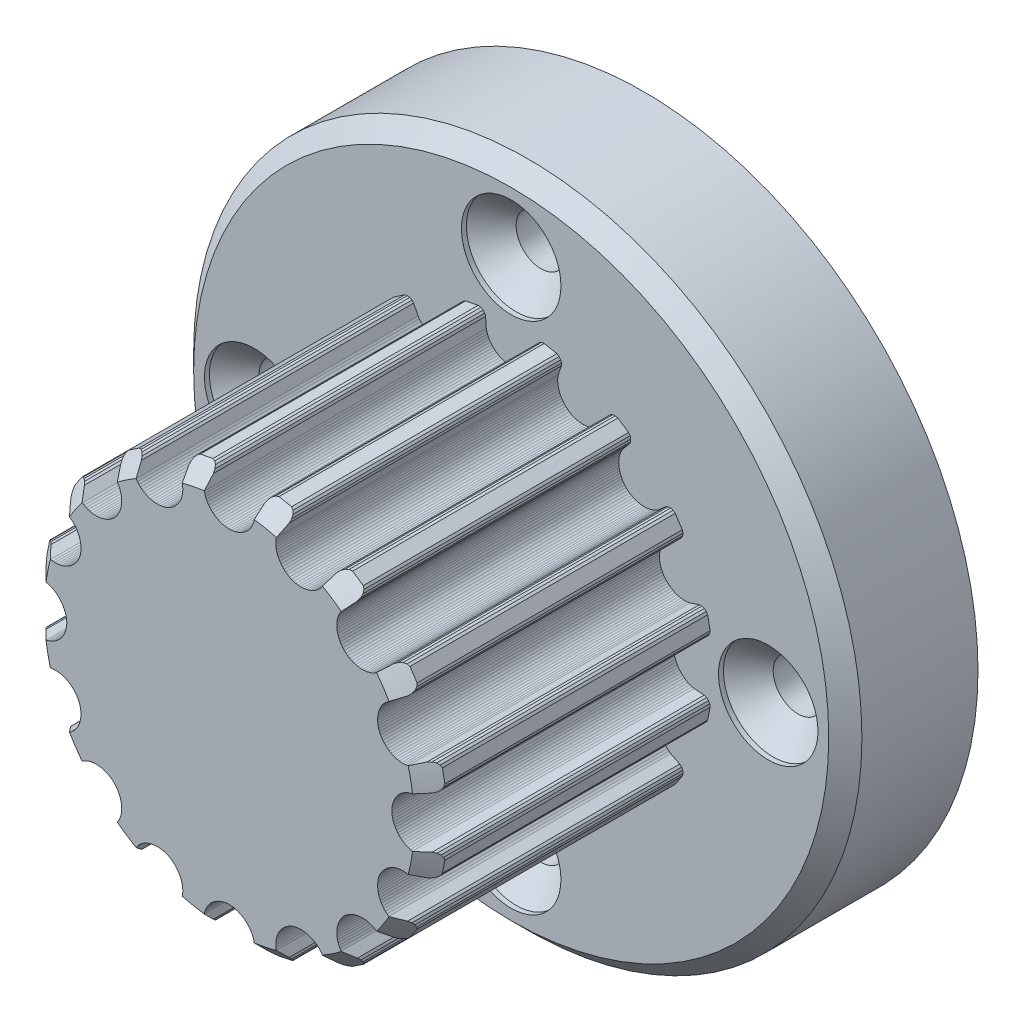
SolidWorks part; units mm, degrees
ref_plane "Front Plane" through (0, 0, 0) normal (0, 0, 1) x (1, 0, 0)
ref_plane "Top Plane" through (0, 0, 0) normal (0, 1, 0) x (1, 0, 0)
ref_plane "Right Plane" through (0, 0, 0) normal (1, 0, 0) x (0, 0, -1)
sketch "Sketch1" plane through (0, 0, 0) normal (0, 0, 1) x (1, 0, 0)
  circle A0 centre (0, 0) radius 15.5
  circle A1 centre (0, 15.5) radius 1.5
  circle A2 centre (15.5, 0) radius 1.5
  circle A3 centre (0, -15.5) radius 1.5
  circle A4 centre (-15.5, 0) radius 1.5
  circle A5 centre (0, 0) radius 20.15
  dimension "D1" = 31
  dimension "D2" = 3
  dimension "D3" = 40.3
extrude "Boss-Extrude1" add sketch "Sketch1" along normal blind 8 contours A5 A4 A0 A1 A2 A3 | A4 A0 A3 A2 A1 region at (0, 0, 0) region at (-19.5801, 0, 0)
sketch "Sketch8" plane through (0, 0, 8) normal (0, 0, 1) x (1, 0, 0)
  line L0 (-1.9904, -11.9969) -> (-1.8333, -11.9702)
  line L1 (-1.8333, -11.9702) -> (-1.6992, -11.8961)
  line L2 (-1.6992, -11.8961) -> (-1.5993, -11.7835)
  line L3 (-1.5993, -11.7835) -> (-1.5446, -11.6413)
  line L4 (-1.5446, -11.6413) -> (-1.5027, -11.0359)
  line L5 (-1.5027, -11.0359) -> (-1.4725, -10.9073)
  line L6 (-1.4725, -10.9073) -> (-1.4313, -10.7834)
  line L7 (-1.4313, -10.7834) -> (-1.3796, -10.6646)
  line L8 (-1.3796, -10.6646) -> (-1.3179, -10.5514)
  line L9 (-1.3179, -10.5514) -> (-1.2467, -10.4444)
  line L10 (-1.2467, -10.4444) -> (-1.1667, -10.3438)
  line L11 (-1.1667, -10.3438) -> (-1.0783, -10.2503)
  line L12 (-1.0783, -10.2503) -> (-0.9822, -10.1642)
  line L13 (-0.9822, -10.1642) -> (-0.8789, -10.086)
  line L14 (-0.8789, -10.086) -> (-0.7689, -10.0162)
  line L15 (-0.7689, -10.0162) -> (-0.6528, -9.9552)
  line L16 (-0.6528, -9.9552) -> (-0.5312, -9.9034)
  line L17 (-0.5312, -9.9034) -> (-0.4045, -9.8614)
  line L18 (-0.4045, -9.8614) -> (-0.2734, -9.8296)
  line L19 (-0.2734, -9.8296) -> (-0.1385, -9.8084)
  line L20 (-0.1385, -9.8084) -> (-0.0002, -9.7984)
  line L21 (-0.0002, -9.7984) -> (0.1382, -9.8084)
  line L22 (0.1382, -9.8084) -> (0.2733, -9.8295)
  line L23 (0.2733, -9.8295) -> (0.4045, -9.8613)
  line L24 (0.4045, -9.8613) -> (0.5312, -9.9032)
  line L25 (0.5312, -9.9032) -> (0.6529, -9.9549)
  line L26 (0.6529, -9.9549) -> (0.7691, -10.0159)
  line L27 (0.7691, -10.0159) -> (0.8791, -10.0858)
  line L28 (0.8791, -10.0858) -> (0.9825, -10.1639)
  line L29 (0.9825, -10.1639) -> (1.0786, -10.25)
  line L30 (1.0786, -10.25) -> (1.1669, -10.3436)
  line L31 (1.1669, -10.3436) -> (1.247, -10.4442)
  line L32 (1.247, -10.4442) -> (1.3181, -10.5512)
  line L33 (1.3181, -10.5512) -> (1.3798, -10.6644)
  line L34 (1.3798, -10.6644) -> (1.4315, -10.7832)
  line L35 (1.4315, -10.7832) -> (1.4726, -10.9072)
  line L36 (1.4726, -10.9072) -> (1.5027, -11.0359)
  line L37 (1.5027, -11.0359) -> (1.5446, -11.6413)
  line L38 (1.5446, -11.6413) -> (1.5993, -11.7835)
  line L39 (1.5993, -11.7835) -> (1.6992, -11.8961)
  line L40 (1.6992, -11.8961) -> (1.8333, -11.9702)
  line L41 (1.8333, -11.9702) -> (1.9904, -11.9969)
  line L42 (1.9904, -11.9969) -> (2.7522, -11.8454)
  line L43 (2.7522, -11.8454) -> (2.8871, -11.7606)
  line L44 (2.8871, -11.7606) -> (2.9825, -11.6408)
  line L45 (2.9825, -11.6408) -> (3.0317, -11.4985)
  line L46 (3.0317, -11.4985) -> (3.0279, -11.3462)
  line L47 (3.0279, -11.3462) -> (2.835, -10.7709)
  line L48 (2.835, -10.7709) -> (2.8136, -10.6405)
  line L49 (2.8136, -10.6405) -> (2.8042, -10.5103)
  line L50 (2.8042, -10.5103) -> (2.8066, -10.3807)
  line L51 (2.8066, -10.3807) -> (2.8203, -10.2526)
  line L52 (2.8203, -10.2526) -> (2.8451, -10.1264)
  line L53 (2.8451, -10.1264) -> (2.8805, -10.0029)
  line L54 (2.8805, -10.0029) -> (2.9264, -9.8827)
  line L55 (2.9264, -9.8827) -> (2.9822, -9.7664)
  line L56 (2.9822, -9.7664) -> (3.0478, -9.6546)
  line L57 (3.0478, -9.6546) -> (3.1227, -9.548)
  line L58 (3.1227, -9.548) -> (3.2066, -9.4472)
  line L59 (3.2066, -9.4472) -> (3.2992, -9.3528)
  line L60 (3.2992, -9.3528) -> (3.4001, -9.2656)
  line L61 (3.4001, -9.2656) -> (3.509, -9.186)
  line L62 (3.509, -9.186) -> (3.6256, -9.1148)
  line L63 (3.6256, -9.1148) -> (3.7495, -9.0526)
  line L64 (3.7495, -9.0526) -> (3.8812, -9.0089)
  line L65 (3.8812, -9.0089) -> (4.0141, -8.9767)
  line L66 (4.0141, -8.9767) -> (4.1474, -8.9558)
  line L67 (4.1474, -8.9558) -> (4.2806, -8.9461)
  line L68 (4.2806, -8.9461) -> (4.4128, -8.9473)
  line L69 (4.4128, -8.9473) -> (4.5435, -8.9592)
  line L70 (4.5435, -8.9592) -> (4.6718, -8.9816)
  line L71 (4.6718, -8.9816) -> (4.7972, -9.0143)
  line L72 (4.7972, -9.0143) -> (4.919, -9.057)
  line L73 (4.919, -9.057) -> (5.0364, -9.1097)
  line L74 (5.0364, -9.1097) -> (5.1488, -9.1719)
  line L75 (5.1488, -9.1719) -> (5.2555, -9.2437)
  line L76 (5.2555, -9.2437) -> (5.3558, -9.3246)
  line L77 (5.3558, -9.3246) -> (5.4491, -9.4146)
  line L78 (5.4491, -9.4146) -> (5.5345, -9.5134)
  line L79 (5.5345, -9.5134) -> (5.6115, -9.6208)
  line L80 (5.6115, -9.6208) -> (5.882, -10.164)
  line L81 (5.882, -10.164) -> (5.9869, -10.2745)
  line L82 (5.9869, -10.2745) -> (6.1223, -10.3403)
  line L83 (6.1223, -10.3403) -> (6.2745, -10.3575)
  line L84 (6.2745, -10.3575) -> (6.4299, -10.322)
  line L85 (6.4299, -10.322) -> (7.0757, -9.8905)
  line L86 (7.0757, -9.8905) -> (7.1679, -9.7605)
  line L87 (7.1679, -9.7605) -> (7.2103, -9.6133)
  line L88 (7.2103, -9.6133) -> (7.2013, -9.4631)
  line L89 (7.2013, -9.4631) -> (7.1394, -9.3238)
  line L90 (7.1394, -9.3238) -> (6.741, -8.8661)
  line L91 (6.741, -8.8661) -> (6.6714, -8.7539)
  line L92 (6.6714, -8.7539) -> (6.6129, -8.6371)
  line L93 (6.6129, -8.6371) -> (6.5655, -8.5165)
  line L94 (6.5655, -8.5165) -> (6.5291, -8.3929)
  line L95 (6.5291, -8.3929) -> (6.5037, -8.2669)
  line L96 (6.5037, -8.2669) -> (6.4892, -8.1392)
  line L97 (6.4892, -8.1392) -> (6.4856, -8.0106)
  line L98 (6.4856, -8.0106) -> (6.4926, -7.8817)
  line L99 (6.4926, -7.8817) -> (6.5104, -7.7534)
  line L100 (6.5104, -7.7534) -> (6.5388, -7.6262)
  line L101 (6.5388, -7.6262) -> (6.5778, -7.501)
  line L102 (6.5778, -7.501) -> (6.6272, -7.3784)
  line L103 (6.6272, -7.3784) -> (6.687, -7.2591)
  line L104 (6.687, -7.2591) -> (6.7572, -7.1439)
  line L105 (6.7572, -7.1439) -> (6.8377, -7.0335)
  line L106 (6.8377, -7.0335) -> (6.9284, -6.9286)
  line L107 (6.9284, -6.9286) -> (7.0333, -6.8378)
  line L108 (7.0333, -6.8378) -> (7.1438, -6.7572)
  line L109 (7.1438, -6.7572) -> (7.259, -6.6869)
  line L110 (7.259, -6.6869) -> (7.3783, -6.627)
  line L111 (7.3783, -6.627) -> (7.5009, -6.5775)
  line L112 (7.5009, -6.5775) -> (7.6262, -6.5385)
  line L113 (7.6262, -6.5385) -> (7.7533, -6.5101)
  line L114 (7.7533, -6.5101) -> (7.8817, -6.4923)
  line L115 (7.8817, -6.4923) -> (8.0105, -6.4852)
  line L116 (8.0105, -6.4852) -> (8.1392, -6.4889)
  line L117 (8.1392, -6.4889) -> (8.2669, -6.5034)
  line L118 (8.2669, -6.5034) -> (8.3929, -6.5288)
  line L119 (8.3929, -6.5288) -> (8.5165, -6.5652)
  line L120 (8.5165, -6.5652) -> (8.6371, -6.6127)
  line L121 (8.6371, -6.6127) -> (8.7539, -6.6713)
  line L122 (8.7539, -6.6713) -> (8.8661, -6.741)
  line L123 (8.8661, -6.741) -> (9.3238, -7.1394)
  line L124 (9.3238, -7.1394) -> (9.4631, -7.2013)
  line L125 (9.4631, -7.2013) -> (9.6133, -7.2103)
  line L126 (9.6133, -7.2103) -> (9.7605, -7.1679)
  line L127 (9.7605, -7.1679) -> (9.8905, -7.0757)
  line L128 (9.8905, -7.0757) -> (10.322, -6.4299)
  line L129 (10.322, -6.4299) -> (10.3575, -6.2745)
  line L130 (10.3575, -6.2745) -> (10.3403, -6.1223)
  line L131 (10.3403, -6.1223) -> (10.2745, -5.9869)
  line L132 (10.2745, -5.9869) -> (10.164, -5.882)
  line L133 (10.164, -5.882) -> (9.6208, -5.6115)
  line L134 (9.6208, -5.6115) -> (9.5135, -5.5345)
  line L135 (9.5135, -5.5345) -> (9.4148, -5.449)
  line L136 (9.4148, -5.449) -> (9.3248, -5.3558)
  line L137 (9.3248, -5.3558) -> (9.2439, -5.2554)
  line L138 (9.2439, -5.2554) -> (9.1722, -5.1487)
  line L139 (9.1722, -5.1487) -> (9.11, -5.0363)
  line L140 (9.11, -5.0363) -> (9.0574, -4.9189)
  line L141 (9.0574, -4.9189) -> (9.0146, -4.7971)
  line L142 (9.0146, -4.7971) -> (8.9819, -4.6717)
  line L143 (8.9819, -4.6717) -> (8.9595, -4.5434)
  line L144 (8.9595, -4.5434) -> (8.9476, -4.4128)
  line L145 (8.9476, -4.4128) -> (8.9463, -4.2806)
  line L146 (8.9463, -4.2806) -> (8.956, -4.1475)
  line L147 (8.956, -4.1475) -> (8.9767, -4.0143)
  line L148 (8.9767, -4.0143) -> (9.0088, -3.8815)
  line L149 (9.0088, -3.8815) -> (9.0524, -3.7498)
  line L150 (9.0524, -3.7498) -> (9.1147, -3.6258)
  line L151 (9.1147, -3.6258) -> (9.1859, -3.5091)
  line L152 (9.1859, -3.5091) -> (9.2654, -3.4)
  line L153 (9.2654, -3.4) -> (9.3527, -3.299)
  line L154 (9.3527, -3.299) -> (9.447, -3.2064)
  line L155 (9.447, -3.2064) -> (9.5478, -3.1224)
  line L156 (9.5478, -3.1224) -> (9.6544, -3.0475)
  line L157 (9.6544, -3.0475) -> (9.7662, -2.9819)
  line L158 (9.7662, -2.9819) -> (9.8826, -2.926)
  line L159 (9.8826, -2.926) -> (10.0028, -2.8802)
  line L160 (10.0028, -2.8802) -> (10.1263, -2.8448)
  line L161 (10.1263, -2.8448) -> (10.2525, -2.82)
  line L162 (10.2525, -2.82) -> (10.3807, -2.8064)
  line L163 (10.3807, -2.8064) -> (10.5102, -2.8041)
  line L164 (10.5102, -2.8041) -> (10.6405, -2.8135)
  line L165 (10.6405, -2.8135) -> (10.7709, -2.835)
  line L166 (10.7709, -2.835) -> (11.3462, -3.0279)
  line L167 (11.3462, -3.0279) -> (11.4985, -3.0317)
  line L168 (11.4985, -3.0317) -> (11.6408, -2.9825)
  line L169 (11.6408, -2.9825) -> (11.7606, -2.8871)
  line L170 (11.7606, -2.8871) -> (11.8454, -2.7522)
  line L171 (11.8454, -2.7522) -> (11.9969, -1.9904)
  line L172 (11.9969, -1.9904) -> (11.9702, -1.8333)
  line L173 (11.9702, -1.8333) -> (11.8961, -1.6992)
  line L174 (11.8961, -1.6992) -> (11.7835, -1.5993)
  line L175 (11.7835, -1.5993) -> (11.6413, -1.5446)
  line L176 (11.6413, -1.5446) -> (11.0359, -1.5027)
  line L177 (11.0359, -1.5027) -> (10.9073, -1.4725)
  line L178 (10.9073, -1.4725) -> (10.7834, -1.4313)
  line L179 (10.7834, -1.4313) -> (10.6646, -1.3796)
  line L180 (10.6646, -1.3796) -> (10.5514, -1.3179)
  line L181 (10.5514, -1.3179) -> (10.4444, -1.2467)
  line L182 (10.4444, -1.2467) -> (10.3438, -1.1667)
  line L183 (10.3438, -1.1667) -> (10.2503, -1.0783)
  line L184 (10.2503, -1.0783) -> (10.1642, -0.9822)
  line L185 (10.1642, -0.9822) -> (10.086, -0.8789)
  line L186 (10.086, -0.8789) -> (10.0162, -0.7689)
  line L187 (10.0162, -0.7689) -> (9.9552, -0.6528)
  line L188 (9.9552, -0.6528) -> (9.9034, -0.5312)
  line L189 (9.9034, -0.5312) -> (9.8614, -0.4045)
  line L190 (9.8614, -0.4045) -> (9.8296, -0.2734)
  line L191 (9.8296, -0.2734) -> (9.8084, -0.1385)
  line L192 (9.8084, -0.1385) -> (9.7984, -0.0002)
  line L193 (9.7984, -0.0002) -> (9.8084, 0.1382)
  line L194 (9.8084, 0.1382) -> (9.8295, 0.2733)
  line L195 (9.8295, 0.2733) -> (9.8613, 0.4045)
  line L196 (9.8613, 0.4045) -> (9.9032, 0.5312)
  line L197 (9.9032, 0.5312) -> (9.9549, 0.6529)
  line L198 (9.9549, 0.6529) -> (10.0159, 0.7691)
  line L199 (10.0159, 0.7691) -> (10.0858, 0.8791)
  line L200 (10.0858, 0.8791) -> (10.1639, 0.9825)
  line L201 (10.1639, 0.9825) -> (10.25, 1.0786)
  line L202 (10.25, 1.0786) -> (10.3436, 1.1669)
  line L203 (10.3436, 1.1669) -> (10.4442, 1.247)
  line L204 (10.4442, 1.247) -> (10.5512, 1.3181)
  line L205 (10.5512, 1.3181) -> (10.6644, 1.3798)
  line L206 (10.6644, 1.3798) -> (10.7832, 1.4315)
  line L207 (10.7832, 1.4315) -> (10.9072, 1.4726)
  line L208 (10.9072, 1.4726) -> (11.0359, 1.5027)
  line L209 (11.0359, 1.5027) -> (11.6413, 1.5446)
  line L210 (11.6413, 1.5446) -> (11.7835, 1.5993)
  line L211 (11.7835, 1.5993) -> (11.8961, 1.6992)
  line L212 (11.8961, 1.6992) -> (11.9702, 1.8333)
  line L213 (11.9702, 1.8333) -> (11.9969, 1.9904)
  line L214 (11.9969, 1.9904) -> (11.8454, 2.7522)
  line L215 (11.8454, 2.7522) -> (11.7606, 2.8871)
  line L216 (11.7606, 2.8871) -> (11.6408, 2.9825)
  line L217 (11.6408, 2.9825) -> (11.4985, 3.0317)
  line L218 (11.4985, 3.0317) -> (11.3462, 3.0279)
  line L219 (11.3462, 3.0279) -> (10.7709, 2.835)
  line L220 (10.7709, 2.835) -> (10.6405, 2.8136)
  line L221 (10.6405, 2.8136) -> (10.5103, 2.8042)
  line L222 (10.5103, 2.8042) -> (10.3807, 2.8066)
  line L223 (10.3807, 2.8066) -> (10.2526, 2.8203)
  line L224 (10.2526, 2.8203) -> (10.1264, 2.8451)
  line L225 (10.1264, 2.8451) -> (10.0029, 2.8805)
  line L226 (10.0029, 2.8805) -> (9.8827, 2.9264)
  line L227 (9.8827, 2.9264) -> (9.7664, 2.9822)
  line L228 (9.7664, 2.9822) -> (9.6546, 3.0478)
  line L229 (9.6546, 3.0478) -> (9.548, 3.1227)
  line L230 (9.548, 3.1227) -> (9.4472, 3.2066)
  line L231 (9.4472, 3.2066) -> (9.3528, 3.2992)
  line L232 (9.3528, 3.2992) -> (9.2656, 3.4001)
  line L233 (9.2656, 3.4001) -> (9.186, 3.509)
  line L234 (9.186, 3.509) -> (9.1148, 3.6256)
  line L235 (9.1148, 3.6256) -> (9.0526, 3.7495)
  line L236 (9.0526, 3.7495) -> (9.0089, 3.8812)
  line L237 (9.0089, 3.8812) -> (8.9767, 4.0141)
  line L238 (8.9767, 4.0141) -> (8.9558, 4.1474)
  line L239 (8.9558, 4.1474) -> (8.9461, 4.2806)
  line L240 (8.9461, 4.2806) -> (8.9473, 4.4128)
  line L241 (8.9473, 4.4128) -> (8.9592, 4.5435)
  line L242 (8.9592, 4.5435) -> (8.9816, 4.6718)
  line L243 (8.9816, 4.6718) -> (9.0143, 4.7972)
  line L244 (9.0143, 4.7972) -> (9.057, 4.919)
  line L245 (9.057, 4.919) -> (9.1097, 5.0364)
  line L246 (9.1097, 5.0364) -> (9.1719, 5.1488)
  line L247 (9.1719, 5.1488) -> (9.2437, 5.2555)
  line L248 (9.2437, 5.2555) -> (9.3246, 5.3558)
  line L249 (9.3246, 5.3558) -> (9.4146, 5.4491)
  line L250 (9.4146, 5.4491) -> (9.5134, 5.5345)
  line L251 (9.5134, 5.5345) -> (9.6208, 5.6115)
  line L252 (9.6208, 5.6115) -> (10.164, 5.882)
  line L253 (10.164, 5.882) -> (10.2745, 5.9869)
  line L254 (10.2745, 5.9869) -> (10.3403, 6.1223)
  line L255 (10.3403, 6.1223) -> (10.3575, 6.2745)
  line L256 (10.3575, 6.2745) -> (10.322, 6.4299)
  line L257 (10.322, 6.4299) -> (9.8905, 7.0757)
  line L258 (9.8905, 7.0757) -> (9.7605, 7.1679)
  line L259 (9.7605, 7.1679) -> (9.6133, 7.2103)
  line L260 (9.6133, 7.2103) -> (9.4631, 7.2013)
  line L261 (9.4631, 7.2013) -> (9.3238, 7.1394)
  line L262 (9.3238, 7.1394) -> (8.8661, 6.741)
  line L263 (8.8661, 6.741) -> (8.7539, 6.6714)
  line L264 (8.7539, 6.6714) -> (8.6371, 6.6129)
  line L265 (8.6371, 6.6129) -> (8.5165, 6.5655)
  line L266 (8.5165, 6.5655) -> (8.3929, 6.5291)
  line L267 (8.3929, 6.5291) -> (8.2669, 6.5037)
  line L268 (8.2669, 6.5037) -> (8.1392, 6.4892)
  line L269 (8.1392, 6.4892) -> (8.0106, 6.4856)
  line L270 (8.0106, 6.4856) -> (7.8817, 6.4926)
  line L271 (7.8817, 6.4926) -> (7.7534, 6.5104)
  line L272 (7.7534, 6.5104) -> (7.6262, 6.5388)
  line L273 (7.6262, 6.5388) -> (7.501, 6.5778)
  line L274 (7.501, 6.5778) -> (7.3784, 6.6272)
  line L275 (7.3784, 6.6272) -> (7.2591, 6.687)
  line L276 (7.2591, 6.687) -> (7.1439, 6.7572)
  line L277 (7.1439, 6.7572) -> (7.0335, 6.8377)
  line L278 (7.0335, 6.8377) -> (6.9286, 6.9284)
  line L279 (6.9286, 6.9284) -> (6.8378, 7.0333)
  line L280 (6.8378, 7.0333) -> (6.7572, 7.1438)
  line L281 (6.7572, 7.1438) -> (6.6869, 7.259)
  line L282 (6.6869, 7.259) -> (6.627, 7.3783)
  line L283 (6.627, 7.3783) -> (6.5775, 7.5009)
  line L284 (6.5775, 7.5009) -> (6.5385, 7.6262)
  line L285 (6.5385, 7.6262) -> (6.5101, 7.7533)
  line L286 (6.5101, 7.7533) -> (6.4923, 7.8817)
  line L287 (6.4923, 7.8817) -> (6.4852, 8.0105)
  line L288 (6.4852, 8.0105) -> (6.4889, 8.1392)
  line L289 (6.4889, 8.1392) -> (6.5034, 8.2669)
  line L290 (6.5034, 8.2669) -> (6.5288, 8.3929)
  line L291 (6.5288, 8.3929) -> (6.5652, 8.5165)
  line L292 (6.5652, 8.5165) -> (6.6127, 8.6371)
  line L293 (6.6127, 8.6371) -> (6.6713, 8.7539)
  line L294 (6.6713, 8.7539) -> (6.741, 8.8661)
  line L295 (6.741, 8.8661) -> (7.1394, 9.3238)
  line L296 (7.1394, 9.3238) -> (7.2013, 9.4631)
  line L297 (7.2013, 9.4631) -> (7.2103, 9.6133)
  line L298 (7.2103, 9.6133) -> (7.1679, 9.7605)
  line L299 (7.1679, 9.7605) -> (7.0757, 9.8905)
  line L300 (7.0757, 9.8905) -> (6.4299, 10.322)
  line L301 (6.4299, 10.322) -> (6.2745, 10.3575)
  line L302 (6.2745, 10.3575) -> (6.1223, 10.3403)
  line L303 (6.1223, 10.3403) -> (5.9869, 10.2745)
  line L304 (5.9869, 10.2745) -> (5.882, 10.164)
  line L305 (5.882, 10.164) -> (5.6115, 9.6208)
  line L306 (5.6115, 9.6208) -> (5.5345, 9.5135)
  line L307 (5.5345, 9.5135) -> (5.449, 9.4148)
  line L308 (5.449, 9.4148) -> (5.3558, 9.3248)
  line L309 (5.3558, 9.3248) -> (5.2554, 9.2439)
  line L310 (5.2554, 9.2439) -> (5.1487, 9.1722)
  line L311 (5.1487, 9.1722) -> (5.0363, 9.11)
  line L312 (5.0363, 9.11) -> (4.9189, 9.0574)
  line L313 (4.9189, 9.0574) -> (4.7971, 9.0146)
  line L314 (4.7971, 9.0146) -> (4.6717, 8.9819)
  line L315 (4.6717, 8.9819) -> (4.5434, 8.9595)
  line L316 (4.5434, 8.9595) -> (4.4128, 8.9476)
  line L317 (4.4128, 8.9476) -> (4.2806, 8.9463)
  line L318 (4.2806, 8.9463) -> (4.1475, 8.956)
  line L319 (4.1475, 8.956) -> (4.0143, 8.9767)
  line L320 (4.0143, 8.9767) -> (3.8815, 9.0088)
  line L321 (3.8815, 9.0088) -> (3.7498, 9.0524)
  line L322 (3.7498, 9.0524) -> (3.6258, 9.1147)
  line L323 (3.6258, 9.1147) -> (3.5091, 9.1859)
  line L324 (3.5091, 9.1859) -> (3.4, 9.2654)
  line L325 (3.4, 9.2654) -> (3.299, 9.3527)
  line L326 (3.299, 9.3527) -> (3.2064, 9.447)
  line L327 (3.2064, 9.447) -> (3.1224, 9.5478)
  line L328 (3.1224, 9.5478) -> (3.0475, 9.6544)
  line L329 (3.0475, 9.6544) -> (2.9819, 9.7662)
  line L330 (2.9819, 9.7662) -> (2.926, 9.8826)
  line L331 (2.926, 9.8826) -> (2.8802, 10.0028)
  line L332 (2.8802, 10.0028) -> (2.8448, 10.1263)
  line L333 (2.8448, 10.1263) -> (2.82, 10.2525)
  line L334 (2.82, 10.2525) -> (2.8064, 10.3807)
  line L335 (2.8064, 10.3807) -> (2.8041, 10.5102)
  line L336 (2.8041, 10.5102) -> (2.8135, 10.6405)
  line L337 (2.8135, 10.6405) -> (2.835, 10.7709)
  line L338 (2.835, 10.7709) -> (3.0279, 11.3462)
  line L339 (3.0279, 11.3462) -> (3.0317, 11.4985)
  line L340 (3.0317, 11.4985) -> (2.9825, 11.6408)
  line L341 (2.9825, 11.6408) -> (2.8871, 11.7606)
  line L342 (2.8871, 11.7606) -> (2.7522, 11.8454)
  line L343 (2.7522, 11.8454) -> (1.9904, 11.9969)
  line L344 (1.9904, 11.9969) -> (1.8333, 11.9702)
  line L345 (1.8333, 11.9702) -> (1.6992, 11.8961)
  line L346 (1.6992, 11.8961) -> (1.5993, 11.7835)
  line L347 (1.5993, 11.7835) -> (1.5446, 11.6413)
  line L348 (1.5446, 11.6413) -> (1.5027, 11.0359)
  line L349 (1.5027, 11.0359) -> (1.4725, 10.9073)
  line L350 (1.4725, 10.9073) -> (1.4313, 10.7834)
  line L351 (1.4313, 10.7834) -> (1.3796, 10.6646)
  line L352 (1.3796, 10.6646) -> (1.3179, 10.5514)
  line L353 (1.3179, 10.5514) -> (1.2467, 10.4444)
  line L354 (1.2467, 10.4444) -> (1.1667, 10.3438)
  line L355 (1.1667, 10.3438) -> (1.0783, 10.2503)
  line L356 (1.0783, 10.2503) -> (0.9822, 10.1642)
  line L357 (0.9822, 10.1642) -> (0.8789, 10.086)
  line L358 (0.8789, 10.086) -> (0.7689, 10.0162)
  line L359 (0.7689, 10.0162) -> (0.6528, 9.9552)
  line L360 (0.6528, 9.9552) -> (0.5312, 9.9034)
  line L361 (0.5312, 9.9034) -> (0.4045, 9.8614)
  line L362 (0.4045, 9.8614) -> (0.2734, 9.8296)
  line L363 (0.2734, 9.8296) -> (0.1385, 9.8084)
  line L364 (0.1385, 9.8084) -> (0.0002, 9.7984)
  line L365 (0.0002, 9.7984) -> (-0.1382, 9.8084)
  line L366 (-0.1382, 9.8084) -> (-0.2733, 9.8295)
  line L367 (-0.2733, 9.8295) -> (-0.4045, 9.8613)
  line L368 (-0.4045, 9.8613) -> (-0.5312, 9.9032)
  line L369 (-0.5312, 9.9032) -> (-0.6529, 9.9549)
  line L370 (-0.6529, 9.9549) -> (-0.7691, 10.0159)
  line L371 (-0.7691, 10.0159) -> (-0.8791, 10.0858)
  line L372 (-0.8791, 10.0858) -> (-0.9825, 10.1639)
  line L373 (-0.9825, 10.1639) -> (-1.0786, 10.25)
  line L374 (-1.0786, 10.25) -> (-1.1669, 10.3436)
  line L375 (-1.1669, 10.3436) -> (-1.247, 10.4442)
  line L376 (-1.247, 10.4442) -> (-1.3181, 10.5512)
  line L377 (-1.3181, 10.5512) -> (-1.3798, 10.6644)
  line L378 (-1.3798, 10.6644) -> (-1.4315, 10.7832)
  line L379 (-1.4315, 10.7832) -> (-1.4726, 10.9072)
  line L380 (-1.4726, 10.9072) -> (-1.5027, 11.0359)
  line L381 (-1.5027, 11.0359) -> (-1.5446, 11.6413)
  line L382 (-1.5446, 11.6413) -> (-1.5993, 11.7835)
  line L383 (-1.5993, 11.7835) -> (-1.6992, 11.8961)
  line L384 (-1.6992, 11.8961) -> (-1.8333, 11.9702)
  line L385 (-1.8333, 11.9702) -> (-1.9904, 11.9969)
  line L386 (-1.9904, 11.9969) -> (-2.7522, 11.8454)
  line L387 (-2.7522, 11.8454) -> (-2.8871, 11.7606)
  line L388 (-2.8871, 11.7606) -> (-2.9825, 11.6408)
  line L389 (-2.9825, 11.6408) -> (-3.0317, 11.4985)
  line L390 (-3.0317, 11.4985) -> (-3.0279, 11.3462)
  line L391 (-3.0279, 11.3462) -> (-2.835, 10.7709)
  line L392 (-2.835, 10.7709) -> (-2.8136, 10.6405)
  line L393 (-2.8136, 10.6405) -> (-2.8042, 10.5103)
  line L394 (-2.8042, 10.5103) -> (-2.8066, 10.3807)
  line L395 (-2.8066, 10.3807) -> (-2.8203, 10.2526)
  line L396 (-2.8203, 10.2526) -> (-2.8451, 10.1264)
  line L397 (-2.8451, 10.1264) -> (-2.8805, 10.0029)
  line L398 (-2.8805, 10.0029) -> (-2.9264, 9.8827)
  line L399 (-2.9264, 9.8827) -> (-2.9822, 9.7664)
  line L400 (-2.9822, 9.7664) -> (-3.0478, 9.6546)
  line L401 (-3.0478, 9.6546) -> (-3.1227, 9.548)
  line L402 (-3.1227, 9.548) -> (-3.2066, 9.4472)
  line L403 (-3.2066, 9.4472) -> (-3.2992, 9.3528)
  line L404 (-3.2992, 9.3528) -> (-3.4001, 9.2656)
  line L405 (-3.4001, 9.2656) -> (-3.509, 9.186)
  line L406 (-3.509, 9.186) -> (-3.6256, 9.1148)
  line L407 (-3.6256, 9.1148) -> (-3.7495, 9.0526)
  line L408 (-3.7495, 9.0526) -> (-3.8812, 9.0089)
  line L409 (-3.8812, 9.0089) -> (-4.0141, 8.9767)
  line L410 (-4.0141, 8.9767) -> (-4.1474, 8.9558)
  line L411 (-4.1474, 8.9558) -> (-4.2806, 8.9461)
  line L412 (-4.2806, 8.9461) -> (-4.4128, 8.9473)
  line L413 (-4.4128, 8.9473) -> (-4.5435, 8.9592)
  line L414 (-4.5435, 8.9592) -> (-4.6718, 8.9816)
  line L415 (-4.6718, 8.9816) -> (-4.7972, 9.0143)
  line L416 (-4.7972, 9.0143) -> (-4.919, 9.057)
  line L417 (-4.919, 9.057) -> (-5.0364, 9.1097)
  line L418 (-5.0364, 9.1097) -> (-5.1488, 9.1719)
  line L419 (-5.1488, 9.1719) -> (-5.2555, 9.2437)
  line L420 (-5.2555, 9.2437) -> (-5.3558, 9.3246)
  line L421 (-5.3558, 9.3246) -> (-5.4491, 9.4146)
  line L422 (-5.4491, 9.4146) -> (-5.5345, 9.5134)
  line L423 (-5.5345, 9.5134) -> (-5.6115, 9.6208)
  line L424 (-5.6115, 9.6208) -> (-5.882, 10.164)
  line L425 (-5.882, 10.164) -> (-5.9869, 10.2745)
  line L426 (-5.9869, 10.2745) -> (-6.1223, 10.3403)
  line L427 (-6.1223, 10.3403) -> (-6.2745, 10.3575)
  line L428 (-6.2745, 10.3575) -> (-6.4299, 10.322)
  line L429 (-6.4299, 10.322) -> (-7.0757, 9.8905)
  line L430 (-7.0757, 9.8905) -> (-7.1679, 9.7605)
  line L431 (-7.1679, 9.7605) -> (-7.2103, 9.6133)
  line L432 (-7.2103, 9.6133) -> (-7.2013, 9.4631)
  line L433 (-7.2013, 9.4631) -> (-7.1394, 9.3238)
  line L434 (-7.1394, 9.3238) -> (-6.741, 8.8661)
  line L435 (-6.741, 8.8661) -> (-6.6714, 8.7539)
  line L436 (-6.6714, 8.7539) -> (-6.6129, 8.6371)
  line L437 (-6.6129, 8.6371) -> (-6.5655, 8.5165)
  line L438 (-6.5655, 8.5165) -> (-6.5291, 8.3929)
  line L439 (-6.5291, 8.3929) -> (-6.5037, 8.2669)
  line L440 (-6.5037, 8.2669) -> (-6.4892, 8.1392)
  line L441 (-6.4892, 8.1392) -> (-6.4856, 8.0106)
  line L442 (-6.4856, 8.0106) -> (-6.4926, 7.8817)
  line L443 (-6.4926, 7.8817) -> (-6.5104, 7.7534)
  line L444 (-6.5104, 7.7534) -> (-6.5388, 7.6262)
  line L445 (-6.5388, 7.6262) -> (-6.5778, 7.501)
  line L446 (-6.5778, 7.501) -> (-6.6272, 7.3784)
  line L447 (-6.6272, 7.3784) -> (-6.687, 7.2591)
  line L448 (-6.687, 7.2591) -> (-6.7572, 7.1439)
  line L449 (-6.7572, 7.1439) -> (-6.8377, 7.0335)
  line L450 (-6.8377, 7.0335) -> (-6.9284, 6.9286)
  line L451 (-6.9284, 6.9286) -> (-7.0333, 6.8378)
  line L452 (-7.0333, 6.8378) -> (-7.1438, 6.7572)
  line L453 (-7.1438, 6.7572) -> (-7.259, 6.6869)
  line L454 (-7.259, 6.6869) -> (-7.3783, 6.627)
  line L455 (-7.3783, 6.627) -> (-7.5009, 6.5775)
  line L456 (-7.5009, 6.5775) -> (-7.6262, 6.5385)
  line L457 (-7.6262, 6.5385) -> (-7.7533, 6.5101)
  line L458 (-7.7533, 6.5101) -> (-7.8817, 6.4923)
  line L459 (-7.8817, 6.4923) -> (-8.0105, 6.4852)
  line L460 (-8.0105, 6.4852) -> (-8.1392, 6.4889)
  line L461 (-8.1392, 6.4889) -> (-8.2669, 6.5034)
  line L462 (-8.2669, 6.5034) -> (-8.3929, 6.5288)
  line L463 (-8.3929, 6.5288) -> (-8.5165, 6.5652)
  line L464 (-8.5165, 6.5652) -> (-8.6371, 6.6127)
  line L465 (-8.6371, 6.6127) -> (-8.7539, 6.6713)
  line L466 (-8.7539, 6.6713) -> (-8.8661, 6.741)
  line L467 (-8.8661, 6.741) -> (-9.3238, 7.1394)
  line L468 (-9.3238, 7.1394) -> (-9.4631, 7.2013)
  line L469 (-9.4631, 7.2013) -> (-9.6133, 7.2103)
  line L470 (-9.6133, 7.2103) -> (-9.7605, 7.1679)
  line L471 (-9.7605, 7.1679) -> (-9.8905, 7.0757)
  line L472 (-9.8905, 7.0757) -> (-10.322, 6.4299)
  line L473 (-10.322, 6.4299) -> (-10.3575, 6.2745)
  line L474 (-10.3575, 6.2745) -> (-10.3403, 6.1223)
  line L475 (-10.3403, 6.1223) -> (-10.2745, 5.9869)
  line L476 (-10.2745, 5.9869) -> (-10.164, 5.882)
  line L477 (-10.164, 5.882) -> (-9.6208, 5.6115)
  line L478 (-9.6208, 5.6115) -> (-9.5135, 5.5345)
  line L479 (-9.5135, 5.5345) -> (-9.4148, 5.449)
  line L480 (-9.4148, 5.449) -> (-9.3248, 5.3558)
  line L481 (-9.3248, 5.3558) -> (-9.2439, 5.2554)
  line L482 (-9.2439, 5.2554) -> (-9.1722, 5.1487)
  line L483 (-9.1722, 5.1487) -> (-9.11, 5.0363)
  line L484 (-9.11, 5.0363) -> (-9.0574, 4.9189)
  line L485 (-9.0574, 4.9189) -> (-9.0146, 4.7971)
  line L486 (-9.0146, 4.7971) -> (-8.9819, 4.6717)
  line L487 (-8.9819, 4.6717) -> (-8.9595, 4.5434)
  line L488 (-8.9595, 4.5434) -> (-8.9476, 4.4128)
  line L489 (-8.9476, 4.4128) -> (-8.9463, 4.2806)
  line L490 (-8.9463, 4.2806) -> (-8.956, 4.1475)
  line L491 (-8.956, 4.1475) -> (-8.9767, 4.0143)
  line L492 (-8.9767, 4.0143) -> (-9.0088, 3.8815)
  line L493 (-9.0088, 3.8815) -> (-9.0524, 3.7498)
  line L494 (-9.0524, 3.7498) -> (-9.1147, 3.6258)
  line L495 (-9.1147, 3.6258) -> (-9.1859, 3.5091)
  line L496 (-9.1859, 3.5091) -> (-9.2654, 3.4)
  line L497 (-9.2654, 3.4) -> (-9.3527, 3.299)
  line L498 (-9.3527, 3.299) -> (-9.447, 3.2064)
  line L499 (-9.447, 3.2064) -> (-9.5478, 3.1224)
  line L500 (-9.5478, 3.1224) -> (-9.6544, 3.0475)
  line L501 (-9.6544, 3.0475) -> (-9.7662, 2.9819)
  line L502 (-9.7662, 2.9819) -> (-9.8826, 2.926)
  line L503 (-9.8826, 2.926) -> (-10.0028, 2.8802)
  line L504 (-10.0028, 2.8802) -> (-10.1263, 2.8448)
  line L505 (-10.1263, 2.8448) -> (-10.2525, 2.82)
  line L506 (-10.2525, 2.82) -> (-10.3807, 2.8064)
  line L507 (-10.3807, 2.8064) -> (-10.5102, 2.8041)
  line L508 (-10.5102, 2.8041) -> (-10.6405, 2.8135)
  line L509 (-10.6405, 2.8135) -> (-10.7709, 2.835)
  line L510 (-10.7709, 2.835) -> (-11.3462, 3.0279)
  line L511 (-11.3462, 3.0279) -> (-11.4985, 3.0317)
  line L512 (-11.4985, 3.0317) -> (-11.6408, 2.9825)
  line L513 (-11.6408, 2.9825) -> (-11.7606, 2.8871)
  line L514 (-11.7606, 2.8871) -> (-11.8454, 2.7522)
  line L515 (-11.8454, 2.7522) -> (-11.9969, 1.9904)
  line L516 (-11.9969, 1.9904) -> (-11.9702, 1.8333)
  line L517 (-11.9702, 1.8333) -> (-11.8961, 1.6992)
  line L518 (-11.8961, 1.6992) -> (-11.7835, 1.5993)
  line L519 (-11.7835, 1.5993) -> (-11.6413, 1.5446)
  line L520 (-11.6413, 1.5446) -> (-11.0359, 1.5027)
  line L521 (-11.0359, 1.5027) -> (-10.9073, 1.4725)
  line L522 (-10.9073, 1.4725) -> (-10.7834, 1.4313)
  line L523 (-10.7834, 1.4313) -> (-10.6646, 1.3796)
  line L524 (-10.6646, 1.3796) -> (-10.5514, 1.3179)
  line L525 (-10.5514, 1.3179) -> (-10.4444, 1.2467)
  line L526 (-10.4444, 1.2467) -> (-10.3438, 1.1667)
  line L527 (-10.3438, 1.1667) -> (-10.2503, 1.0783)
  line L528 (-10.2503, 1.0783) -> (-10.1642, 0.9822)
  line L529 (-10.1642, 0.9822) -> (-10.086, 0.8789)
  line L530 (-10.086, 0.8789) -> (-10.0162, 0.7689)
  line L531 (-10.0162, 0.7689) -> (-9.9552, 0.6528)
  line L532 (-9.9552, 0.6528) -> (-9.9034, 0.5312)
  line L533 (-9.9034, 0.5312) -> (-9.8614, 0.4045)
  line L534 (-9.8614, 0.4045) -> (-9.8296, 0.2734)
  line L535 (-9.8296, 0.2734) -> (-9.8084, 0.1385)
  line L536 (-9.8084, 0.1385) -> (-9.7984, 0.0002)
  line L537 (-9.7984, 0.0002) -> (-9.8084, -0.1382)
  line L538 (-9.8084, -0.1382) -> (-9.8295, -0.2733)
  line L539 (-9.8295, -0.2733) -> (-9.8613, -0.4045)
  line L540 (-9.8613, -0.4045) -> (-9.9032, -0.5312)
  line L541 (-9.9032, -0.5312) -> (-9.9549, -0.6529)
  line L542 (-9.9549, -0.6529) -> (-10.0159, -0.7691)
  line L543 (-10.0159, -0.7691) -> (-10.0858, -0.8791)
  line L544 (-10.0858, -0.8791) -> (-10.1639, -0.9825)
  line L545 (-10.1639, -0.9825) -> (-10.25, -1.0786)
  line L546 (-10.25, -1.0786) -> (-10.3436, -1.1669)
  line L547 (-10.3436, -1.1669) -> (-10.4442, -1.247)
  line L548 (-10.4442, -1.247) -> (-10.5512, -1.3181)
  line L549 (-10.5512, -1.3181) -> (-10.6644, -1.3798)
  line L550 (-10.6644, -1.3798) -> (-10.7832, -1.4315)
  line L551 (-10.7832, -1.4315) -> (-10.9072, -1.4726)
  line L552 (-10.9072, -1.4726) -> (-11.0359, -1.5027)
  line L553 (-11.0359, -1.5027) -> (-11.6413, -1.5446)
  line L554 (-11.6413, -1.5446) -> (-11.7835, -1.5993)
  line L555 (-11.7835, -1.5993) -> (-11.8961, -1.6992)
  line L556 (-11.8961, -1.6992) -> (-11.9702, -1.8333)
  line L557 (-11.9702, -1.8333) -> (-11.9969, -1.9904)
  line L558 (-11.9969, -1.9904) -> (-11.8454, -2.7522)
  line L559 (-11.8454, -2.7522) -> (-11.7606, -2.8871)
  line L560 (-11.7606, -2.8871) -> (-11.6408, -2.9825)
  line L561 (-11.6408, -2.9825) -> (-11.4985, -3.0317)
  line L562 (-11.4985, -3.0317) -> (-11.3462, -3.0279)
  line L563 (-11.3462, -3.0279) -> (-10.7709, -2.835)
  line L564 (-10.7709, -2.835) -> (-10.6405, -2.8136)
  line L565 (-10.6405, -2.8136) -> (-10.5103, -2.8042)
  line L566 (-10.5103, -2.8042) -> (-10.3807, -2.8066)
  line L567 (-10.3807, -2.8066) -> (-10.2526, -2.8203)
  line L568 (-10.2526, -2.8203) -> (-10.1264, -2.8451)
  line L569 (-10.1264, -2.8451) -> (-10.0029, -2.8805)
  line L570 (-10.0029, -2.8805) -> (-9.8827, -2.9264)
  line L571 (-9.8827, -2.9264) -> (-9.7664, -2.9822)
  line L572 (-9.7664, -2.9822) -> (-9.6546, -3.0478)
  line L573 (-9.6546, -3.0478) -> (-9.548, -3.1227)
  line L574 (-9.548, -3.1227) -> (-9.4472, -3.2066)
  line L575 (-9.4472, -3.2066) -> (-9.3528, -3.2992)
  line L576 (-9.3528, -3.2992) -> (-9.2656, -3.4001)
  line L577 (-9.2656, -3.4001) -> (-9.186, -3.509)
  line L578 (-9.186, -3.509) -> (-9.1148, -3.6256)
  line L579 (-9.1148, -3.6256) -> (-9.0526, -3.7495)
  line L580 (-9.0526, -3.7495) -> (-9.0089, -3.8812)
  line L581 (-9.0089, -3.8812) -> (-8.9767, -4.0141)
  line L582 (-8.9767, -4.0141) -> (-8.9558, -4.1474)
  line L583 (-8.9558, -4.1474) -> (-8.9461, -4.2806)
  line L584 (-8.9461, -4.2806) -> (-8.9473, -4.4128)
  line L585 (-8.9473, -4.4128) -> (-8.9592, -4.5435)
  line L586 (-8.9592, -4.5435) -> (-8.9816, -4.6718)
  line L587 (-8.9816, -4.6718) -> (-9.0143, -4.7972)
  line L588 (-9.0143, -4.7972) -> (-9.057, -4.919)
  line L589 (-9.057, -4.919) -> (-9.1097, -5.0364)
  line L590 (-9.1097, -5.0364) -> (-9.1719, -5.1488)
  line L591 (-9.1719, -5.1488) -> (-9.2437, -5.2555)
  line L592 (-9.2437, -5.2555) -> (-9.3246, -5.3558)
  line L593 (-9.3246, -5.3558) -> (-9.4146, -5.4491)
  line L594 (-9.4146, -5.4491) -> (-9.5134, -5.5345)
  line L595 (-9.5134, -5.5345) -> (-9.6208, -5.6115)
  line L596 (-9.6208, -5.6115) -> (-10.164, -5.882)
  line L597 (-10.164, -5.882) -> (-10.2745, -5.9869)
  line L598 (-10.2745, -5.9869) -> (-10.3403, -6.1223)
  line L599 (-10.3403, -6.1223) -> (-10.3575, -6.2745)
  line L600 (-10.3575, -6.2745) -> (-10.322, -6.4299)
  line L601 (-10.322, -6.4299) -> (-9.8905, -7.0757)
  line L602 (-9.8905, -7.0757) -> (-9.7605, -7.1679)
  line L603 (-9.7605, -7.1679) -> (-9.6133, -7.2103)
  line L604 (-9.6133, -7.2103) -> (-9.4631, -7.2013)
  line L605 (-9.4631, -7.2013) -> (-9.3238, -7.1394)
  line L606 (-9.3238, -7.1394) -> (-8.8661, -6.741)
  line L607 (-8.8661, -6.741) -> (-8.7539, -6.6714)
  line L608 (-8.7539, -6.6714) -> (-8.6371, -6.6129)
  line L609 (-8.6371, -6.6129) -> (-8.5165, -6.5655)
  line L610 (-8.5165, -6.5655) -> (-8.3929, -6.5291)
  line L611 (-8.3929, -6.5291) -> (-8.2669, -6.5037)
  line L612 (-8.2669, -6.5037) -> (-8.1392, -6.4892)
  line L613 (-8.1392, -6.4892) -> (-8.0106, -6.4856)
  line L614 (-8.0106, -6.4856) -> (-7.8817, -6.4926)
  line L615 (-7.8817, -6.4926) -> (-7.7534, -6.5104)
  line L616 (-7.7534, -6.5104) -> (-7.6262, -6.5388)
  line L617 (-7.6262, -6.5388) -> (-7.501, -6.5778)
  line L618 (-7.501, -6.5778) -> (-7.3784, -6.6272)
  line L619 (-7.3784, -6.6272) -> (-7.2591, -6.687)
  line L620 (-7.2591, -6.687) -> (-7.1439, -6.7572)
  line L621 (-7.1439, -6.7572) -> (-7.0335, -6.8377)
  line L622 (-7.0335, -6.8377) -> (-6.9286, -6.9284)
  line L623 (-6.9286, -6.9284) -> (-6.8378, -7.0333)
  line L624 (-6.8378, -7.0333) -> (-6.7572, -7.1438)
  line L625 (-6.7572, -7.1438) -> (-6.6869, -7.259)
  line L626 (-6.6869, -7.259) -> (-6.627, -7.3783)
  line L627 (-6.627, -7.3783) -> (-6.5775, -7.5009)
  line L628 (-6.5775, -7.5009) -> (-6.5385, -7.6262)
  line L629 (-6.5385, -7.6262) -> (-6.5101, -7.7533)
  line L630 (-6.5101, -7.7533) -> (-6.4923, -7.8817)
  line L631 (-6.4923, -7.8817) -> (-6.4852, -8.0105)
  line L632 (-6.4852, -8.0105) -> (-6.4889, -8.1392)
  line L633 (-6.4889, -8.1392) -> (-6.5034, -8.2669)
  line L634 (-6.5034, -8.2669) -> (-6.5288, -8.3929)
  line L635 (-6.5288, -8.3929) -> (-6.5652, -8.5165)
  line L636 (-6.5652, -8.5165) -> (-6.6127, -8.6371)
  line L637 (-6.6127, -8.6371) -> (-6.6713, -8.7539)
  line L638 (-6.6713, -8.7539) -> (-6.741, -8.8661)
  line L639 (-6.741, -8.8661) -> (-7.1394, -9.3238)
  line L640 (-7.1394, -9.3238) -> (-7.2013, -9.4631)
  line L641 (-7.2013, -9.4631) -> (-7.2103, -9.6133)
  line L642 (-7.2103, -9.6133) -> (-7.1679, -9.7605)
  line L643 (-7.1679, -9.7605) -> (-7.0757, -9.8905)
  line L644 (-7.0757, -9.8905) -> (-6.4299, -10.322)
  line L645 (-6.4299, -10.322) -> (-6.2745, -10.3575)
  line L646 (-6.2745, -10.3575) -> (-6.1223, -10.3403)
  line L647 (-6.1223, -10.3403) -> (-5.9869, -10.2745)
  line L648 (-5.9869, -10.2745) -> (-5.882, -10.164)
  line L649 (-5.882, -10.164) -> (-5.6115, -9.6208)
  line L650 (-5.6115, -9.6208) -> (-5.5345, -9.5135)
  line L651 (-5.5345, -9.5135) -> (-5.449, -9.4148)
  line L652 (-5.449, -9.4148) -> (-5.3558, -9.3248)
  line L653 (-5.3558, -9.3248) -> (-5.2554, -9.2439)
  line L654 (-5.2554, -9.2439) -> (-5.1487, -9.1722)
  line L655 (-5.1487, -9.1722) -> (-5.0363, -9.11)
  line L656 (-5.0363, -9.11) -> (-4.9189, -9.0574)
  line L657 (-4.9189, -9.0574) -> (-4.7971, -9.0146)
  line L658 (-4.7971, -9.0146) -> (-4.6717, -8.9819)
  line L659 (-4.6717, -8.9819) -> (-4.5434, -8.9595)
  line L660 (-4.5434, -8.9595) -> (-4.4128, -8.9476)
  line L661 (-4.4128, -8.9476) -> (-4.2806, -8.9463)
  line L662 (-4.2806, -8.9463) -> (-4.1475, -8.956)
  line L663 (-4.1475, -8.956) -> (-4.0143, -8.9767)
  line L664 (-4.0143, -8.9767) -> (-3.8815, -9.0088)
  line L665 (-3.8815, -9.0088) -> (-3.7498, -9.0524)
  line L666 (-3.7498, -9.0524) -> (-3.6258, -9.1147)
  line L667 (-3.6258, -9.1147) -> (-3.5091, -9.1859)
  line L668 (-3.5091, -9.1859) -> (-3.4, -9.2654)
  line L669 (-3.4, -9.2654) -> (-3.299, -9.3527)
  line L670 (-3.299, -9.3527) -> (-3.2064, -9.447)
  line L671 (-3.2064, -9.447) -> (-3.1224, -9.5478)
  line L672 (-3.1224, -9.5478) -> (-3.0475, -9.6544)
  line L673 (-3.0475, -9.6544) -> (-2.9819, -9.7662)
  line L674 (-2.9819, -9.7662) -> (-2.926, -9.8826)
  line L675 (-2.926, -9.8826) -> (-2.8802, -10.0028)
  line L676 (-2.8802, -10.0028) -> (-2.8448, -10.1263)
  line L677 (-2.8448, -10.1263) -> (-2.82, -10.2525)
  line L678 (-2.82, -10.2525) -> (-2.8064, -10.3807)
  line L679 (-2.8064, -10.3807) -> (-2.8041, -10.5102)
  line L680 (-2.8041, -10.5102) -> (-2.8135, -10.6405)
  line L681 (-2.8135, -10.6405) -> (-2.835, -10.7709)
  line L682 (-2.835, -10.7709) -> (-3.0279, -11.3462)
  line L683 (-3.0279, -11.3462) -> (-3.0317, -11.4985)
  line L684 (-3.0317, -11.4985) -> (-2.9825, -11.6408)
  line L685 (-2.9825, -11.6408) -> (-2.8871, -11.7606)
  line L686 (-2.8871, -11.7606) -> (-2.7522, -11.8454)
  line L687 (-2.7522, -11.8454) -> (-1.9904, -11.9969)
extrude "Boss-Extrude3" add sketch "Sketch8" along normal blind 17
sketch "Sketch9" plane through (0, 0, 0) normal (0, 0, -1) x (-1, 0, 0)
  circle A0 centre (0, 0) radius 1.5
  dimension "D1" = 3
extrude "Cut-Extrude1" cut sketch "Sketch9" against normal blind 6.25
hole_wizard "CSK for M3 Flat Head Machine Screw1" positions "Sketch10" profile "Sketch12" countersink size "M3" standard "ANSI Metric" end condition up to next
sketch "Sketch10" plane through (0, 0, 8) normal (0, 0, 1) x (1, 0, 0)
  point P0 (0, 15.5)
  point P3 (15.5, 0)
  point P6 (0, -15.5)
  point P9 (-15.5, 0)
sketch "Sketch12" plane through (0, 15.5, 8) normal (1, 0, 0) x (0, -1, 0)
  line L0 (0, 0) -> (0, 8)
  line L1 (0, 8) -> (1.5, 8)
  line L2 (1.5, 8) -> (1.5, 1.8)
  line L3 (1.5, 1.8) -> (3, 0.3)
  line L4 (3, 0.3) -> (3, 0)
  line L6 (3, 0) -> (0, 0)
  line L7 (-1.5, 1.8) -> (-3, 0.3) construction
  line L11 (0, -6.35) -> (0, 107.95) construction
  dimension "Thru Hole Dia." = 3
  dimension "Thru Hole Depth" = 8
  dimension "C'Sink Dia." = 6
  dimension "C'Sink Angle" = 90
  dimension "Head Clearance" = 0.3
chamfer "Chamfer1" distance 1 angle 45 1 edges at (20.15, 0, 8)
ref_axis "Axis1" through (0, 0, 33.6588) along (0, 0, -1)
ref_plane "Plane5" through (0, 0, 0) normal (0.1951, 0.9808, 0) x (0.9808, -0.1951, 0)
sketch "Sketch13" plane through (0, 0, 0) normal (0.1951, 0.9808, 0) x (0, 0, -1)
  line L4 (-25, 12.6547) -> (-25, 11.1547)
  line L5 (-25, 11.1547) -> (-23.5, 12.6547)
  line L7 (-23.5, 12.6547) -> (-25, 12.6547)
  line L8 (-25, 12.1547) -> (-8, 12.1547) construction
  point P3 (0, 0)
  point P7 (0, 0)
  point P8 (0, 0)
  point P12 (0, 0)
  dimension "D1" = 1.5
  dimension "D2" = 0.5
revolve "Cut-Revolve4" cut sketch "Sketch13" angle 360 about axis through (0, 0, 33.6588) along (0, 0, -1)
equation "\"D3@Sketch1\"=20.15*2"
equation "\"TEETH\"= 16"
equation "\"PITCH\"= 5mm"
equation "\"C\"= \"TEETH\" * \"PITCH\""
equation "\"RADIUS\"= \"C\" / ( 2 * PI )"
